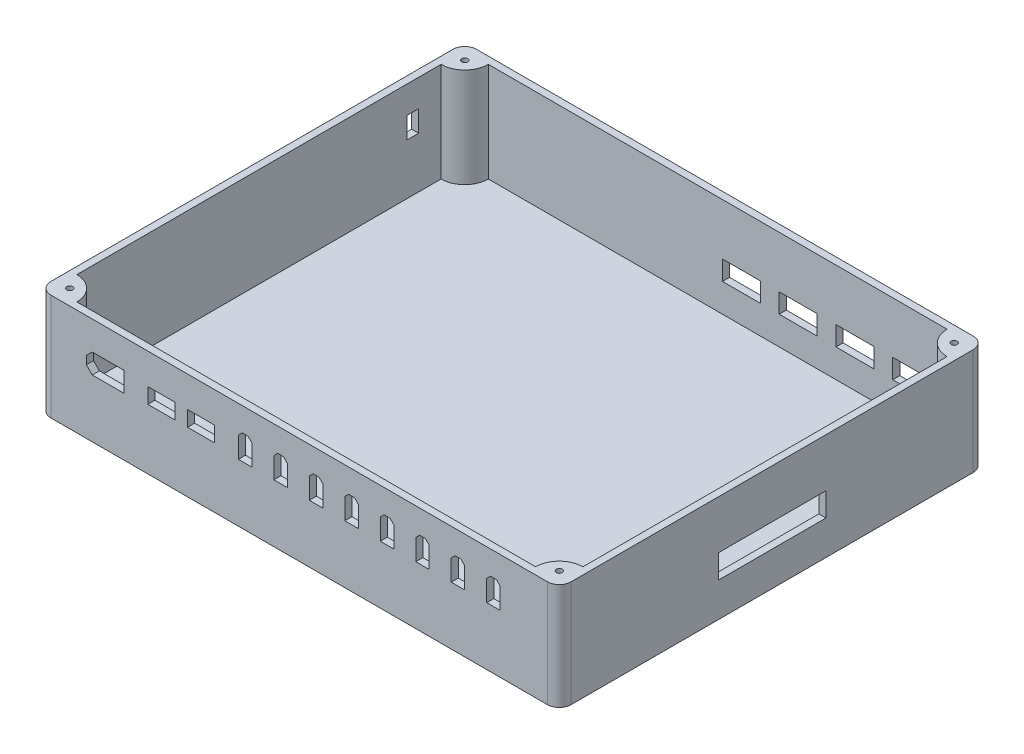
SolidWorks part; units mm, degrees
ref_plane "Front Plane" through (0, 0, 0) normal (0, 0, 1) x (1, 0, 0)
ref_plane "Top Plane" through (0, 0, 0) normal (0, 1, 0) x (1, 0, 0)
ref_plane "Right Plane" through (0, 0, 0) normal (1, 0, 0) x (0, 0, -1)
sketch "Sketch1" plane through (0, 0, 0) normal (0, 1, 0) x (1, 0, 0)
  line L1 (0, 0) -> (220, 0)
  line L2 (0, 0) -> (0, 180)
  line L3 (0, 180) -> (220, 180)
  line L4 (220, 0) -> (220, 180)
  dimension "D1" = 220
  dimension "D2" = 180
extrude "Boss-Extrude1" add sketch "Sketch1" along normal blind 45
fillet "Fillet1" radius 5 4 edges at (0, 22.5, -180) (0, 22.5, 0) (220, 22.5, -180) (220, 22.5, 0)
sketch "Sketch7" plane through (0, 45, 0) normal (0, 1, 0) x (1, 0, 0)
  line L0 (110, 187.4123) -> (110, -2.139) construction
  line L1 (-6.8646, 90) -> (231.1986, 90) construction
  line L2 (207, 177) -> (13, 177)
  line L3 (217, 167) -> (217, 13)
  line L4 (215, 180) -> (5, 180) construction
  line L5 (220, 5) -> (220, 175) construction
  line L6 (207, 3) -> (13, 3)
  line L7 (3, 167) -> (3, 13)
  line L8 (0, 175) -> (0, 5) construction
  line L9 (5, 0) -> (215, 0) construction
  arc A0 (207, 177) -> (217, 167) centre (217, 177) ccw
  arc A1 (207, 3) -> (217, 13) centre (217, 3) cw
  arc A2 (13, 3) -> (3, 13) centre (3, 3) ccw
  arc A3 (13, 177) -> (3, 167) centre (3, 177) cw
  point P14 (217, 90)
  point P18 (110, 3)
  point P23 (110, 177)
  dimension "D5" = 3
  dimension "D1" = 3
  dimension "D2" = 3
  dimension "D3" = 13
  dimension "D4" = 13
  dimension "D6" = 3
extrude "Cut-Extrude7" cut sketch "Sketch7" against normal blind 42
sketch "Sketch2" plane through (0, 0, 0) normal (0, 0, 1) x (1, 0, 0)
  line L0 (175.9, 35) -> (178.4, 35)
  line L1 (190.9, 35) -> (193.4, 35)
  line L2 (189.3, 33.4) -> (189.3, 24.5)
  line L3 (189.3, 24.5) -> (195, 24.5)
  line L4 (195, 33.4) -> (195, 24.5)
  line L5 (174.3, 33.4) -> (174.3, 24.5)
  line L6 (174.3, 24.5) -> (180, 24.5)
  line L7 (180, 33.4) -> (180, 24.5)
  line L8 (160.9, 35) -> (163.4, 35)
  line L9 (159.3, 33.4) -> (159.3, 24.5)
  line L10 (159.3, 24.5) -> (165, 24.5)
  line L11 (165, 33.4) -> (165, 24.5)
  line L12 (145.9, 35) -> (148.4, 35)
  line L13 (144.3, 33.4) -> (144.3, 24.5)
  line L14 (144.3, 24.5) -> (150, 24.5)
  line L15 (150, 33.4) -> (150, 24.5)
  line L16 (130.9, 35) -> (133.4, 35)
  line L17 (129.3, 33.4) -> (129.3, 24.5)
  line L18 (129.3, 24.5) -> (135, 24.5)
  line L19 (135, 33.4) -> (135, 24.5)
  line L20 (115.9, 35) -> (118.4, 35)
  line L21 (114.3, 33.4) -> (114.3, 24.5)
  line L22 (114.3, 24.5) -> (120, 24.5)
  line L23 (120, 33.4) -> (120, 24.5)
  line L24 (100.9, 35) -> (103.4, 35)
  line L25 (99.3, 33.4) -> (99.3, 24.5)
  line L26 (99.3, 24.5) -> (105, 24.5)
  line L27 (105, 33.4) -> (105, 24.5)
  line L28 (85.9, 35) -> (88.4, 35)
  line L29 (84.3, 33.4) -> (84.3, 24.5)
  line L30 (84.3, 24.5) -> (90, 24.5)
  line L31 (90, 33.4) -> (90, 24.5)
  line L33 (215, 0) -> (215, 45) construction
  line L35 (189.3, 33.4) -> (190.9, 35)
  line L36 (193.4, 35) -> (195, 33.4)
  line L37 (178.4, 35) -> (180, 33.4)
  line L38 (174.3, 33.4) -> (175.9, 35)
  line L39 (163.4, 35) -> (165, 33.4)
  line L40 (159.3, 33.4) -> (160.9, 35)
  line L41 (144.3, 33.4) -> (145.9, 35)
  line L42 (148.4, 35) -> (150, 33.4)
  line L43 (133.4, 35) -> (135, 33.4)
  line L44 (129.3, 33.4) -> (130.9, 35)
  line L45 (118.4, 35) -> (120, 33.4)
  line L46 (114.3, 33.4) -> (115.9, 35)
  line L47 (103.4, 35) -> (105, 33.4)
  line L48 (99.3, 33.4) -> (100.9, 35)
  line L49 (88.4, 35) -> (90, 33.4)
  line L50 (84.3, 33.4) -> (85.9, 35)
  point P0 (189.3, 35)
  point P3 (195, 35)
  point P6 (174.3, 35)
  point P9 (180, 35)
  point P10 (159.3, 35)
  point P13 (165, 35)
  point P14 (144.3, 35)
  point P17 (150, 35)
  point P18 (129.3, 35)
  point P21 (135, 35)
  point P22 (114.3, 35)
  point P25 (120, 35)
  point P26 (99.3, 35)
  point P29 (105, 35)
  point P30 (84.3, 35)
  point P33 (90, 35)
  dimension "D1" = 5.7
  dimension "D2" = 10.5
  dimension "D5" = 20
  dimension "D6" = 1.6
  dimension "D7" = 45
  dimension "D8" = 1.6
  dimension "D9" = 45
  dimension "D10" = 1.6
  dimension "D11" = 45
  dimension "D12" = 1.6
  dimension "D13" = 45
  dimension "D14" = 1.6
  dimension "D15" = 45
  dimension "D16" = 1.6
  dimension "D17" = 45
  dimension "D18" = 1.6
  dimension "D19" = 45
  dimension "D20" = 1.6
  dimension "D21" = 45
  dimension "D22" = 1.6
  dimension "D23" = 45
  dimension "D24" = 1.6
  dimension "D25" = 45
  dimension "D26" = 1.6
  dimension "D27" = 45
  dimension "D28" = 1.6
  dimension "D29" = 45
  dimension "D30" = 1.6
  dimension "D31" = 45
  dimension "D32" = 1.6
  dimension "D33" = 45
  dimension "D34" = 1.6
  dimension "D35" = 45
  dimension "D36" = 1.6
  dimension "D37" = 45
sketch "Sketch3" plane through (0, 0, 0) normal (0, 0, 1) x (1, 0, 0)
  line L0 (22.5, 32.9) -> (36, 32.9)
  line L1 (20, 30.4) -> (20, 27)
  line L2 (22.5, 24.5) -> (36, 24.5)
  line L3 (36, 32.9) -> (36, 24.5)
  line L4 (20, 30.4) -> (22.5, 32.9)
  line L5 (20, 27) -> (22.5, 24.5)
  line L6 (5, 0) -> (215, 0) construction
  line L7 (5, 45) -> (5, 0) construction
  point P0 (20, 32.9)
  point P2 (20, 24.5)
  dimension "D1" = 8.4
  dimension "D2" = 16
  dimension "D3" = 16
  dimension "D4" = 2.5
  dimension "D5" = 45
  dimension "D6" = 2.5
  dimension "D7" = 45
  dimension "D8" = 24.5
  dimension "D9" = 15
extrude "Cut-Extrude2" cut sketch "Sketch2" against normal blind 5
extrude "Cut-Extrude3" cut sketch "Sketch3" against normal blind 5
sketch "Sketch4" plane through (0, 0, 0) normal (0, 0, 1) x (1, 0, 0)
  line L0 (5, 0) -> (215, 0) construction
  line L1 (46, 25.5) -> (57.5, 25.5)
  line L2 (46, 25.5) -> (46, 32)
  line L3 (46, 32) -> (57.5, 32)
  line L4 (57.5, 25.5) -> (57.5, 32)
  line L5 (62.8, 25.5) -> (74.3, 25.5)
  line L6 (62.8, 25.5) -> (62.8, 32)
  line L7 (62.8, 32) -> (74.3, 32)
  line L8 (74.3, 25.5) -> (74.3, 32)
  line L9 (50.0473, 25.5) -> (65.0473, 25.5) construction
  line L10 (36, 24.5) -> (36, 32.9) construction
  line L11 (84.3, 33.4) -> (84.3, 24.5) construction
  dimension "D1" = 6.5
  dimension "D2" = 11.5
  dimension "D3" = 25.5
  dimension "D5" = 15
  dimension "D6" = 10
  dimension "D7" = 6.5
  dimension "D8" = 10
  dimension "D4" = 2
extrude "Cut-Extrude4" cut sketch "Sketch4" against normal blind 5
sketch "Sketch5" plane through (220, 0, 0) normal (1, 0, 0) x (0, 0, -1)
  line L0 (175, 0) -> (175, 45) construction
  line L5 (67.2316, 14.4802) -> (112.7684, 14.4802)
  line L7 (67.2316, 14.4802) -> (67.2316, 24.4802)
  line L8 (67.2316, 24.4802) -> (112.7684, 24.4802)
  line L9 (112.7684, 14.4802) -> (112.7684, 24.4802)
  line L10 (5, 45) -> (5, 0) construction
  dimension "D2" = 10
  dimension "D4" = 17.8646
extrude "Cut-Extrude5" cut sketch "Sketch5" against normal blind 5
sketch "Sketch6" plane through (0, 0, -180) normal (0, 0, -1) x (-1, 0, 0)
  line L0 (-215, 45) -> (-215, 0) construction
  line L1 (-200, 23.2) -> (-184, 23.2)
  line L2 (-200, 23.2) -> (-200, 15)
  line L3 (-200, 15) -> (-184, 15)
  line L4 (-184, 23.2) -> (-184, 15)
  line L5 (-215, 0) -> (-5, 0) construction
  line L6 (-176, 23.2) -> (-160, 23.2)
  line L7 (-176, 23.2) -> (-176, 15)
  line L8 (-176, 15) -> (-160, 15)
  line L9 (-160, 23.2) -> (-160, 15)
  line L10 (-152, 23.2) -> (-136, 23.2)
  line L11 (-152, 23.2) -> (-152, 15)
  line L12 (-152, 15) -> (-136, 15)
  line L13 (-136, 23.2) -> (-136, 15)
  line L14 (-128, 23.2) -> (-112, 23.2)
  line L15 (-128, 23.2) -> (-128, 15)
  line L16 (-128, 15) -> (-112, 15)
  line L17 (-112, 23.2) -> (-112, 15)
  line L18 (-200, 23.2) -> (-176, 23.2) construction
  dimension "D1" = 16
  dimension "D2" = 8.2
  dimension "D3" = 15
  dimension "D4" = 15
  dimension "D6" = 24
  dimension "D5" = 4
extrude "Cut-Extrude6" cut sketch "Sketch6" against normal blind 5
sketch "Sketch8" plane through (0, 0, 0) normal (-1, 0, 0) x (0, 0, 1)
  line L0 (-175, 0) -> (-5, 0) construction
  line L1 (-157.5384, 33.5) -> (-152.5384, 33.5)
  line L2 (-157.5384, 33.5) -> (-157.5384, 24.5)
  line L3 (-157.5384, 24.5) -> (-152.5384, 24.5)
  line L4 (-152.5384, 33.5) -> (-152.5384, 24.5)
  dimension "D1" = 9
  dimension "D2" = 5
  dimension "D3" = 24.5
extrude "Cut-Extrude8" cut sketch "Sketch8" against normal blind 4.2
sketch "Sketch10" plane through (0, 45, 0) normal (0, 1, 0) x (1, 0, 0)
  line L0 (110, 184.9025) -> (110, -6.3644) construction
  line L1 (-9.396, 90) -> (224.0695, 90) construction
  line L2 (0, 175) -> (0, 5) construction
  line L3 (110, -4.9025) -> (110, 186.3644) construction
  line L5 (215, 180) -> (5, 180) construction
  circle A0 centre (6.5, 173.5) radius 1.25
  circle A1 centre (213.5, 173.5) radius 1.25
  circle A2 centre (213.5, 6.5) radius 1.25
  circle A3 centre (6.5, 6.5) radius 1.25
  dimension "D1" = 6.5
  dimension "D2" = 6.5
extrude "Cut-Extrude9" cut sketch "Sketch10" against normal blind 40
equation "\"D8@Sketch4\"=\"D6@Sketch4\""
